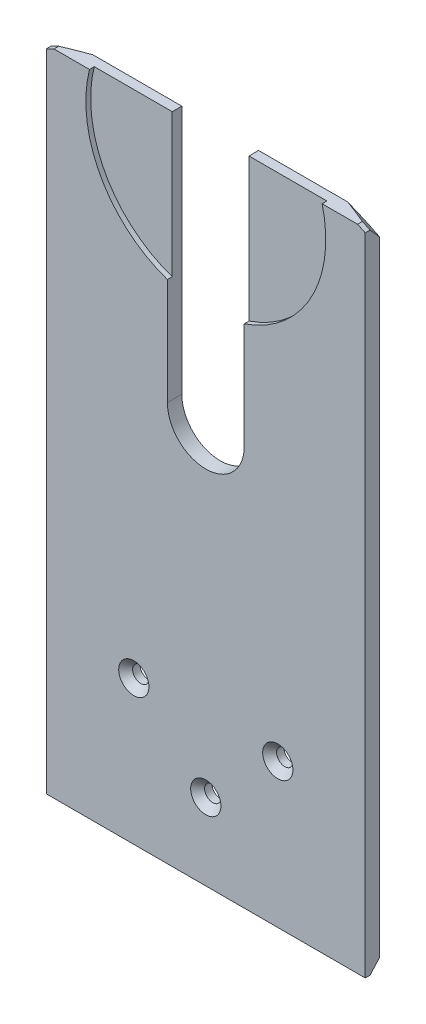
SolidWorks part; units mm, degrees
material "PET"
ref_plane "Front Plane" through (0, 0, 0) normal (0, 0, 1) x (1, 0, 0)
ref_plane "Top Plane" through (0, 0, 0) normal (0, 1, 0) x (1, 0, 0)
ref_plane "Right Plane" through (0, 0, 0) normal (1, 0, 0) x (0, 0, -1)
sketch "Sketch1" plane through (0, 0, 0) normal (0, 0, 1) x (1, 0, 0)
  line L1 (-33.2265, -67.2384) -> (-33.2265, -65) construction
  line L2 (-33.2265, -67.2384) -> (33.2265, -67.2384)
  line L4 (-31.6386, 68) -> (31.6386, 68)
  line L5 (-33.2265, -65) -> (33.2265, -65) construction
  line L6 (82.5, 0) -> (-82.5, 0) construction
  arc A4 (33.2265, -65) -> (26.5518, 68) centre (0, 0) ccw construction
  arc A6 (-31.6386, 68) -> (-33.2265, -67.2384) centre (0, 0) ccw
  arc A7 (-26.5518, 68) -> (-33.2265, -65) centre (0, 0) ccw construction
  arc A8 (33.2265, -67.2384) -> (31.6386, 68) centre (0, 0) ccw
  dimension "D2" = 150
  dimension "D3" = 146
  dimension "D9" = 68
  dimension "D11" = 65
extrude "Boss-Extrude2" add sketch "Sketch1" along normal blind 3
sketch "Sketch2" plane through (0, 0, 3) normal (0, 0, 1) x (1, 0, 0)
  line L0 (0, -2.2) -> (0, 2.2) construction
  line L2 (-33.2265, -67.2384) -> (33.2265, -67.2384) construction
  point P3 (-15, -37.2384)
  point P6 (0, -51.2384)
  point P13 (15, -37.2384)
  dimension "D1" = 30
  dimension "D2" = 14
  dimension "D3" = 16
hole_wizard "CSK for M3 Countersunk Flat Head Screw1" positions "Sketch2" profile "Sketch3" countersink size "M3" standard "ISO" end condition up to next
sketch "Sketch3" plane through (-15, -37.2384, 3) normal (1, 0, 0) x (0, -1, 0)
  line L0 (0, 0) -> (0, 3)
  line L1 (0, 3) -> (1.7, 3)
  line L2 (1.7, 3) -> (1.7, 1.45)
  line L3 (1.7, 1.45) -> (3.15, 0)
  line L5 (3.15, 0) -> (0, 0)
  line L6 (-1.7, 1.45) -> (-3.15, 0) construction
  line L11 (0, -6.35) -> (0, 107.95) construction
  dimension "Thru Hole Dia." = 3.4
  dimension "Thru Hole Depth" = 3
  dimension "Near C'Sink Dia." = 6.3
  dimension "Near C'Sink Angle" = 90
sketch "Sketch4" plane through (0, 0, 3) normal (0, 0, 1) x (1, 0, 0)
  line L0 (0, -2.2) -> (0, 2.2) construction
  line L8 (-8, 16) -> (-8, 68)
  line L9 (-8, 68) -> (8, 68)
  line L10 (8, 16) -> (8, 68)
  line L12 (31.6386, 68) -> (-31.6386, 68) construction
  arc A0 (-8, 16) -> (8, 16) centre (0, 16) ccw
  point P3 (0, 8)
  dimension "D1" = 8
  dimension "D2" = 60
extrude "Cut-Extrude1" cut sketch "Sketch4" against normal up to next contours L8 A0 L10 region at (0, 38.8311, 3)
sketch "Sketch5" plane through (0, 0, 3) normal (0, 0, 1) x (1, 0, 0)
  circle A0 centre (0, 61.9) radius 25
  dimension "D1" = 50
  dimension "D2" = 61.9
extrude "Cut-Extrude2" cut sketch "Sketch5" against normal blind 1
chamfer "Chamfer3" distance 2 2 edges at (-74.9948, 0.8806, 0) (74.9948, 0.8806, 0) tangent propagation no
sketch "Sketch6" plane through (0, 0, 0) normal (0, 0, 1) x (1, 0, 0)
  line L0 (-33.2265, -67.2384) -> (-33.2265, 68)
  line L1 (-33.2265, 68) -> (33.2265, 68)
  line L2 (33.2265, 68) -> (33.2265, -67.2384)
  line L3 (33.2265, -67.2384) -> (-33.2265, -67.2384)
  line L4 (31.6386, 68) -> (24.2444, 68) construction
  line L5 (-33.2265, -67.2384) -> (33.2265, -67.2384) construction
  point P10 (-23.0047, -67.2384)
  point P11 (-33.2265, -67.2384)
extrude "Cut-Extrude3" cut sketch "Sketch6" along normal through all flip side to cut
